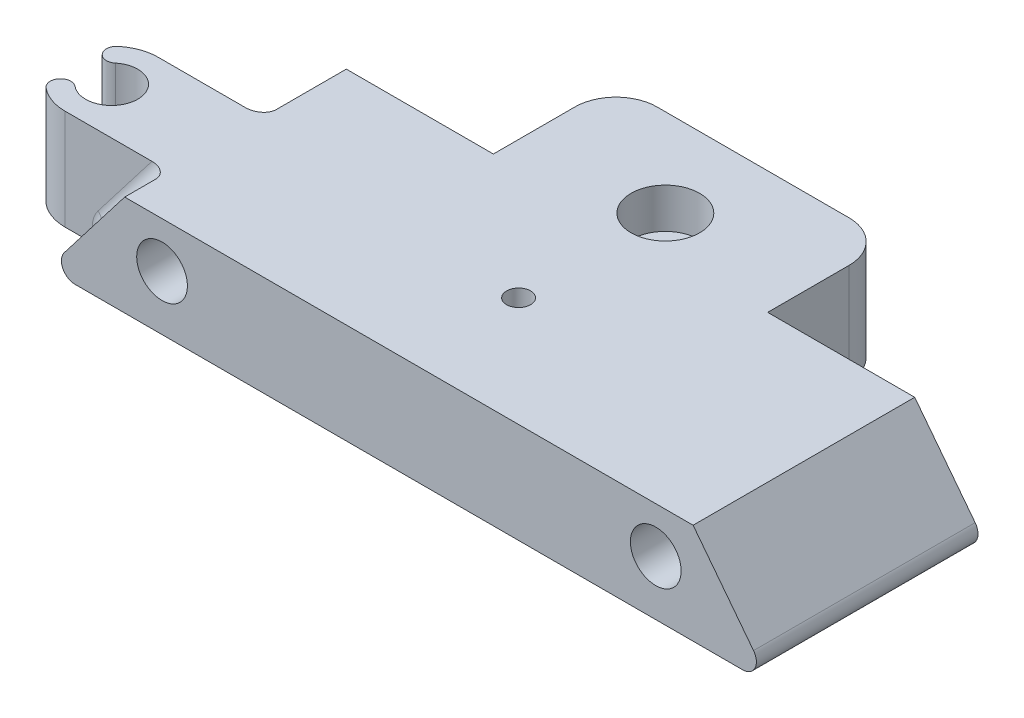
SolidWorks part; units mm, degrees
ref_plane "Front Plane" through (0, 0, 0) normal (0, 0, 1) x (1, 0, 0)
ref_plane "Top Plane" through (0, 0, 0) normal (0, 1, 0) x (1, 0, 0)
ref_plane "Right Plane" through (0, 0, 0) normal (1, 0, 0) x (0, 0, -1)
sketch "Sketch1" plane through (0, 0, 0) normal (0, 1, 0) x (1, 0, 0)
  line L0 (-10.0004, -2.54) -> (10.0004, -2.54) construction
  line L1 (-10.0004, -2.54) -> (10.0004, -2.54)
  line L2 (16, -2.54) -> (20, -2.54) construction
  line L3 (16, -2.54) -> (20, -2.54)
  line L5 (26.925, -8.15) -> (26.925, 0) construction
  line L7 (-26.925, 0) -> (-26.925, -8.15) construction
  line L8 (-20, -2.54) -> (-16, -2.54) construction
  line L9 (-20, -2.54) -> (-16, -2.54)
  line L10 (26.925, -8.15) -> (26.925, 0)
  line L11 (-26.925, 0) -> (-26.925, -8.15)
  line L12 (1.8552, -13.973) -> (2.6903, -2.3287)
  line L13 (-2.6903, -2.3287) -> (-1.8552, -13.973)
  line L14 (1.8552, -13.973) -> (2.6903, -2.3287)
  line L15 (-2.6903, -2.3287) -> (-1.8552, -13.973)
  circle A0 centre (0, -10.7) radius 1 construction
  circle A1 centre (0, -10.7) radius 1
  arc A4 (2.8496, -1.8547) -> (2.6903, -2.3287) centre (3.6877, -2.4002) ccw
  arc A5 (2.8496, -1.8547) -> (-2.8496, -1.8547) centre (0, 0) ccw
  arc A6 (-2.6903, -2.3287) -> (-2.8496, -1.8547) centre (-3.6877, -2.4002) ccw
  arc A7 (-1.8552, -13.973) -> (1.8552, -13.973) centre (0, -13.84) ccw
  arc A8 (2.8496, -1.8547) -> (2.6903, -2.3287) centre (3.6877, -2.4002) ccw
  arc A9 (2.8496, -1.8547) -> (-2.8496, -1.8547) centre (0, 0) ccw
  arc A10 (-2.6903, -2.3287) -> (-2.8496, -1.8547) centre (-3.6877, -2.4002) ccw
  arc A11 (-1.8552, -13.973) -> (1.8552, -13.973) centre (0, -13.84) ccw
  point P23 (0, 0)
  dimension "D1" = 0
ref_plane "Plane1" through (0, 4.425, 0) normal (0, -1, 0) x (-1, 0, 0)
ref_plane "Plane2" through (0, -2.9, 0) normal (0, -1, 0) x (-1, 0, 0)
ref_plane "Plane3" through (0, 0, 2.54) normal (0, 0, 1) x (1, 0, 0)
sketch "Sketch2" plane through (0, 0, 2.54) normal (0, 0, 1) x (1, 0, 0)
  circle A0 centre (-18, 1.1) radius 2 construction
  circle A1 centre (18, 1.1) radius 2 construction
  circle A2 centre (-18, 1.1) radius 2
  circle A3 centre (18, 1.1) radius 2
sketch "Sketch4" plane through (0, 0, 0) normal (0, 1, 0) x (1, 0, 0)
  line L0 (26.925, -8.15) -> (26.925, 0) construction
  line L1 (-26.925, -2.54) -> (-10.0004, -2.54)
  line L2 (-26.925, -2.54) -> (-26.925, -18.7)
  line L3 (-26.925, -18.7) -> (26.925, -18.7)
  line L4 (26.925, -2.54) -> (26.925, -18.7)
  line L5 (-10.0004, -2.54) -> (10.0004, -2.54) construction
  line L6 (-26.925, 0) -> (-26.925, -8.15) construction
  line L7 (10.0004, -2.54) -> (10.0004, 6.4)
  line L8 (10.0004, 6.4) -> (-10.0004, 6.4)
  line L9 (-10.0004, 6.4) -> (-10.0004, -2.54)
  line L10 (10.0004, -2.54) -> (26.925, -2.54)
  arc A0 (-1.8552, -13.973) -> (1.8552, -13.973) centre (0, -13.84) ccw construction
  arc A1 (-1.8552, -13.973) -> (1.8552, -13.973) centre (0, -13.84) ccw construction
  arc A2 (2.8496, -1.8547) -> (-2.8496, -1.8547) centre (0, 0) ccw construction
  point P13 (0, -15.7)
  point P17 (0, 3.4)
  dimension "D1" = 3
  dimension "D2" = 3
extrude "Boss-Extrude1" add sketch "Sketch4" along normal up to surface (4.425 mm away) and the other way up to surface (2.9 mm away) up to plane "Plane1" other way up to plane "Plane2"
sketch "Sketch5" plane through (0, 0, 0) normal (0, 1, 0) x (1, 0, 0)
  line L0 (1.8552, -13.973) -> (2.6903, -2.3287) construction
  line L1 (-2.6903, -2.3287) -> (-1.8552, -13.973) construction
  line L2 (1.8552, -13.973) -> (2.6903, -2.3287) construction
  line L3 (-2.6903, -2.3287) -> (-1.8552, -13.973) construction
  line L4 (2.0049, -13.9838) -> (2.8399, -2.3394)
  line L5 (-2.8399, -2.3394) -> (-2.0049, -13.9838)
  arc A0 (-1.8552, -13.973) -> (1.8552, -13.973) centre (0, -13.84) ccw construction
  arc A1 (-2.6903, -2.3287) -> (-2.8496, -1.8547) centre (-3.6877, -2.4002) ccw construction
  arc A2 (2.8496, -1.8547) -> (2.6903, -2.3287) centre (3.6877, -2.4002) ccw construction
  arc A3 (2.8496, -1.8547) -> (-2.8496, -1.8547) centre (0, 0) ccw construction
  arc A4 (-1.8552, -13.973) -> (1.8552, -13.973) centre (0, -13.84) ccw construction
  arc A5 (-2.6903, -2.3287) -> (-2.8496, -1.8547) centre (-3.6877, -2.4002) ccw construction
  arc A6 (2.8496, -1.8547) -> (2.6903, -2.3287) centre (3.6877, -2.4002) ccw construction
  arc A7 (2.8496, -1.8547) -> (-2.8496, -1.8547) centre (0, 0) ccw construction
  arc A8 (2.9753, -1.9365) -> (2.8399, -2.3394) centre (3.6877, -2.4002) ccw
  arc A9 (2.9753, -1.9365) -> (-2.9753, -1.9365) centre (0, 0) ccw
  arc A10 (-2.8399, -2.3394) -> (-2.9753, -1.9365) centre (-3.6877, -2.4002) ccw
  arc A11 (-2.0049, -13.9838) -> (2.0049, -13.9838) centre (0, -13.84) ccw
  dimension "D1" = 0.15
extrude "Cut-Extrude1" cut sketch "Sketch5" against normal through all
sketch "Sketch6" plane through (0, 4.425, 0) normal (0, 1, 0) x (1, 0, 0)
  circle A0 centre (0, 0) radius 1.3
  dimension "D1" = 2.6
extrude "Cut-Extrude2" cut sketch "Sketch6" against normal through all
sketch "Sketch7" plane through (0, 4.425, 0) normal (0, 1, 0) x (1, 0, 0)
  circle A0 centre (0, 0) radius 2.5
  dimension "D1" = 5
extrude "Cut-Extrude3" cut sketch "Sketch7" against normal offset from surface (2.925 mm away) 1.5 up to face at (0, 0, 1.3)
sketch "Sketch8" plane through (0, 0, 0) normal (0, -1, 0) x (1, 0, 0)
  circle A0 centre (0, 10.7) radius 0.875
  dimension "D1" = 1.75
extrude "Cut-Extrude4" cut sketch "Sketch8" against normal through all
sketch "Sketch9" plane through (0, 0, 2.54) normal (0, 0, -1) x (-1, 0, 0)
  circle A0 centre (18, 1.1) radius 1.85
  circle A1 centre (-18, 1.1) radius 1.85
  dimension "D1" = 3.7
extrude "Cut-Extrude5" cut sketch "Sketch9" against normal through all
sketch "Sketch10" plane through (0, 0, 18.7) normal (0, 0, 1) x (1, 0, 0)
  line L0 (-22.1244, 3.0179) -> (-20.7551, 4.7934) construction
  line L1 (20.7551, 4.7934) -> (22.1244, 3.0179) construction
  line L2 (-22.1244, 3.0179) -> (-20.7551, 4.7934)
  line L3 (20.7551, 4.7934) -> (22.1244, 3.0179)
sketch "Sketch11" plane through (0, 0, 18.7) normal (0, 0, 1) x (1, 0, 0)
  line L0 (-20.7235, 4.425) -> (-26.3726, -2.9)
  line L1 (-22.1244, 3.0179) -> (-20.7551, 4.7934) construction
  line L2 (-26.925, -2.9) -> (26.925, -2.9) construction
  line L3 (-26.925, 4.425) -> (-26.925, -2.9) construction
  line L4 (26.925, 4.425) -> (-26.925, 4.425) construction
  line L5 (-26.925, -2.9) -> (-26.3726, -2.9)
  line L6 (-26.925, 4.425) -> (-26.925, -2.9)
  line L7 (-20.7235, 4.425) -> (-26.925, 4.425)
  line L8 (0, 5.6937) -> (0, -5.6937) construction
  line L9 (20.7235, 4.425) -> (26.925, 4.425)
  line L10 (26.925, 4.425) -> (26.925, -2.9)
  line L11 (26.925, -2.9) -> (26.3726, -2.9)
  line L12 (20.7235, 4.425) -> (26.3726, -2.9)
  point P10 (0, 0)
  point P11 (0, -5.6937)
  dimension "D1" = 0.25
extrude "Cut-Extrude6" cut sketch "Sketch11" against normal through all
fillet "Fillet1" radius 1 2 edges at (-26.3726, -2.9, 10.62) (26.3726, -2.9, 10.62)
fillet "Fillet2" radius 3 2 edges at (-10.0004, 0.7625, -6.4) (10.0004, 0.7625, -6.4)
sketch "Sketch12" plane through (0, 4.425, 0) normal (0, 1, 0) x (1, 0, 0)
  line L0 (-22.1244, -8.15) -> (-20.7551, -8.15) construction
  line L1 (-22.1244, -8.15) -> (-20.7551, -8.15)
  line L2 (-23.1478, -10) -> (-20.7235, -10) construction
  line L3 (-23.1478, -10) -> (-20.7235, -10)
  line L4 (-26.6269, -8.15) -> (-25.2, -35) construction
  line L5 (-26.6269, -8.15) -> (-25.2, -35)
sketch "Sketch13" plane through (0, 4.425, 0) normal (0, 1, 0) x (1, 0, 0)
  line L0 (-20.7235, -2.54) -> (-20.7235, -18.7) construction
  line L1 (-20.7235, -2.54) -> (-20.7235, -18.7)
  line L2 (-20.7235, -8.65) -> (-26.6003, -8.65)
  line L3 (-26.6269, -8.15) -> (-25.2, -35) construction
  line L4 (-22.1244, -8.15) -> (-20.7551, -8.15) construction
  line L5 (-28.3223, -12.05) -> (-37.9123, -12.05) construction
  line L6 (-33.1173, -10.75) -> (-33.1173, -13.35) construction
  line L7 (-28.3223, -10.75) -> (-37.9123, -10.75) construction
  line L8 (-28.3223, -13.35) -> (-37.9123, -13.35) construction
  circle A0 centre (-28.3223, -12.05) radius 1.9
  circle A1 centre (-28.3223, -12.05) radius 3.4
  circle A2 centre (-30.0016, -10) radius 0.75
  circle A3 centre (-30.0016, -14.1) radius 0.75
  point P15 (-33.1173, -12.05)
  point P16 (-33.1173, -12.05)
  point P21 (-33.1173, -10.75)
  point P22 (-33.1173, -13.35)
  dimension "D2" = 3.8
  dimension "D1" = 0.5
  dimension "D4" = 2.6
  dimension "D3" = 1.5
sketch "Sketch14" plane through (0, 4.425, 0) normal (0, 1, 0) x (1, 0, 0)
  line L0 (-20.7235, -8.65) -> (-26.6003, -8.65) construction
  line L1 (-20.7235, -2.54) -> (-20.7235, -18.7) construction
  line L2 (-20.7235, -8.65) -> (-28.3223, -8.65)
  line L3 (-20.7235, -8.65) -> (-20.7235, -15.45)
  line L4 (-20.7235, -15.45) -> (-28.3223, -15.45)
  arc A0 (-28.3223, -8.65) -> (-30.4769, -9.4198) centre (-28.3223, -12.05) ccw
  circle A1 centre (-28.3223, -12.05) radius 3.4
  arc A2 (-30.4769, -14.6802) -> (-28.3223, -15.45) centre (-28.3223, -12.05) ccw
  circle A3 centre (-28.3223, -12.05) radius 1.9
  arc A4 (-29.5263, -13.5198) -> (-29.5263, -10.5802) centre (-28.3223, -12.05) ccw
  circle A5 centre (-30.0016, -14.1) radius 0.75
  arc A6 (-29.5263, -13.5198) -> (-30.4769, -14.6802) centre (-30.0016, -14.1) ccw
  circle A7 centre (-30.0016, -10) radius 0.75
  arc A8 (-30.4769, -9.4198) -> (-29.5263, -10.5802) centre (-30.0016, -10) ccw
  dimension "D1" = 0
  dimension "D2" = 0
  dimension "D3" = 0
  dimension "D4" = 0
extrude "Boss-Extrude2" add sketch "Sketch14" against normal through all
fillet "Fillet3" radius 1 4 edges at (-25.236, -2.3412, 8.65) (-25.236, -2.3412, 15.45) (-22.927, 1.5678, 8.65) (-22.927, 1.5678, 15.45)
